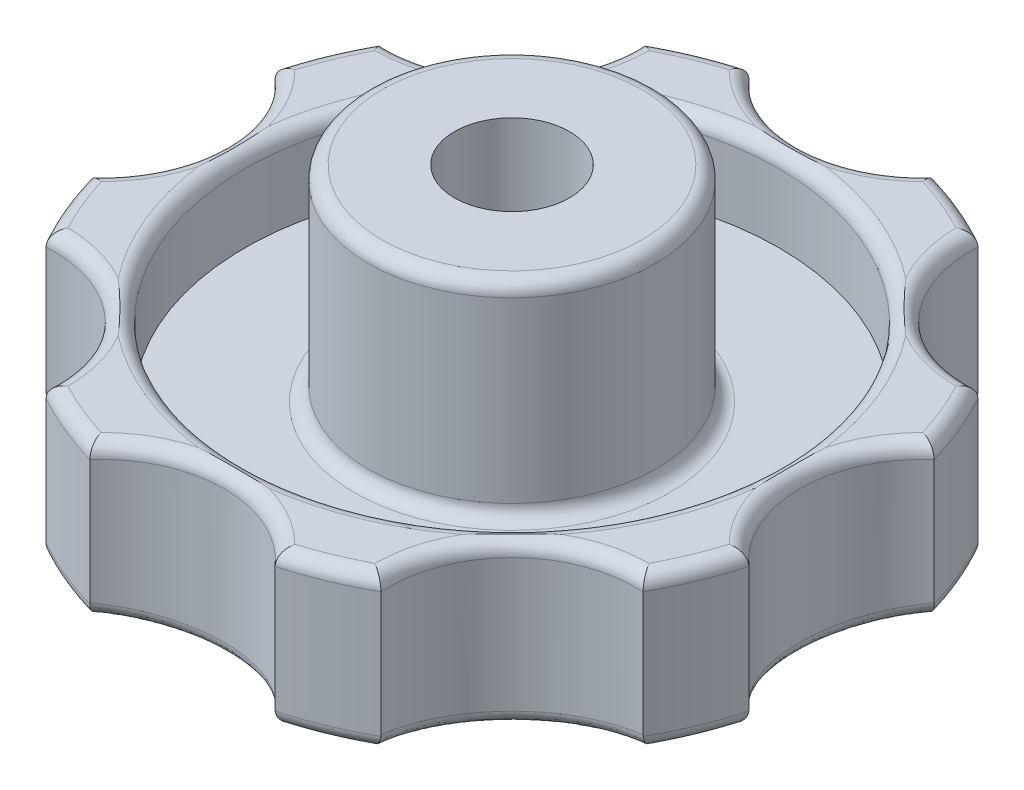
SolidWorks part; units mm, degrees
ref_plane "Front Plane" through (0, 0, 0) normal (0, 0, 1) x (1, 0, 0)
ref_plane "Top Plane" through (0, 0, 0) normal (0, 1, 0) x (1, 0, 0)
ref_plane "Right Plane" through (0, 0, 0) normal (1, 0, 0) x (0, 0, -1)
sketch "Sketch1" plane through (0, 0, 0) normal (0, 0, 1) x (1, 0, 0)
  line L0 (0, 66.2304) -> (0, -55.4031) construction
  line L1 (0, 0) -> (-0.0075, 0)
  line L2 (-25, 2) -> (-25, 13)
  line L3 (-25, 13) -> (-19.5, 13)
  line L4 (-19.5, 13) -> (-19.5, 7)
  line L5 (-19.5, 7) -> (-10.5, 7)
  line L6 (-10.5, 7) -> (-10.5, 22)
  line L7 (-10.5, 22) -> (0, 22)
  spline S0 degree 2 poles (0, 0) (-12.586, 0.0031) (-25, 2) knots 0 0 0 1 1 1
  dimension "D1" = 22
  dimension "D2" = 21
  dimension "D3" = 50
  dimension "D4" = 39
  dimension "D5" = 6
  dimension "D6" = 13
  dimension "D7" = 2
revolve "Revolve4" add sketch "Sketch1" angle 360 about L0 region at (-9.851, 9.2193, 0)
sketch "Sketch2" plane through (0, 22, 0) normal (0, 1, 0) x (1, 0, 0)
  circle A0 centre (0, 0) radius 4.2
  dimension "D1" = 8.4
extrude "Cut-Extrude1" cut sketch "Sketch2" against normal through all
sketch "Sketch3" plane through (0, 13, 0) normal (0, 1, 0) x (1, 0, 0)
  circle A0 centre (0, 30) radius 9
  circle A1 centre (21.2132, 21.2132) radius 9
  circle A2 centre (30, 0) radius 9
  circle A3 centre (21.2132, -21.2132) radius 9
  circle A4 centre (0, -30) radius 9
  circle A5 centre (-21.2132, -21.2132) radius 9
  circle A6 centre (-30, 0) radius 9
  circle A7 centre (-21.2132, 21.2132) radius 9
  point P19 (0, 0)
  dimension "D1" = 18
  dimension "D2" = 30
  dimension "D3" = 8
extrude "Cut-Extrude2" cut sketch "Sketch3" against normal through all
fillet "Fillet1" radius 1 17 edges at (-21.1354, 1.435, 1.5555) (-23.097, 2, 9.5671) (-13.8451, 1.435, 16.0449) (-9.5671, 2, 23.097) (1.5555, 1.435, 21.1354) (9.5671, 2, 23.097) (16.0449, 1.435, 13.8451) (23.097, 2, 9.5671) (21.1354, 1.435, -1.5555) (23.097, 2, -9.5671) (13.8451, 1.435, -16.0449) (9.5671, 2, -23.097) (-1.5555, 1.435, -21.1354) (-9.5671, 2, -23.097) (-16.0449, 1.435, -13.8451) (-23.097, 2, -9.5671) (0, 0.0567, 4.2)
fillet "Fillet2" radius 1 19 edges at (0, 13, -21) (9.5671, 13, -23.097) (14.8492, 13, -14.8492) (23.097, 13, -9.5671) (21, 13, 0) (23.097, 13, 9.5671) (14.8492, 13, 14.8492) (9.5671, 13, 23.097) (0, 13, 21) (-9.5671, 13, 23.097) (-14.8492, 13, 14.8492) (-23.097, 13, 9.5671) (-21, 13, 0) (-23.097, 13, -9.5671) (-14.8492, 13, -14.8492) (-9.5671, 13, -23.097) (0, 13, 19.5) (0, 7, 10.5) (0, 22, 10.5)
